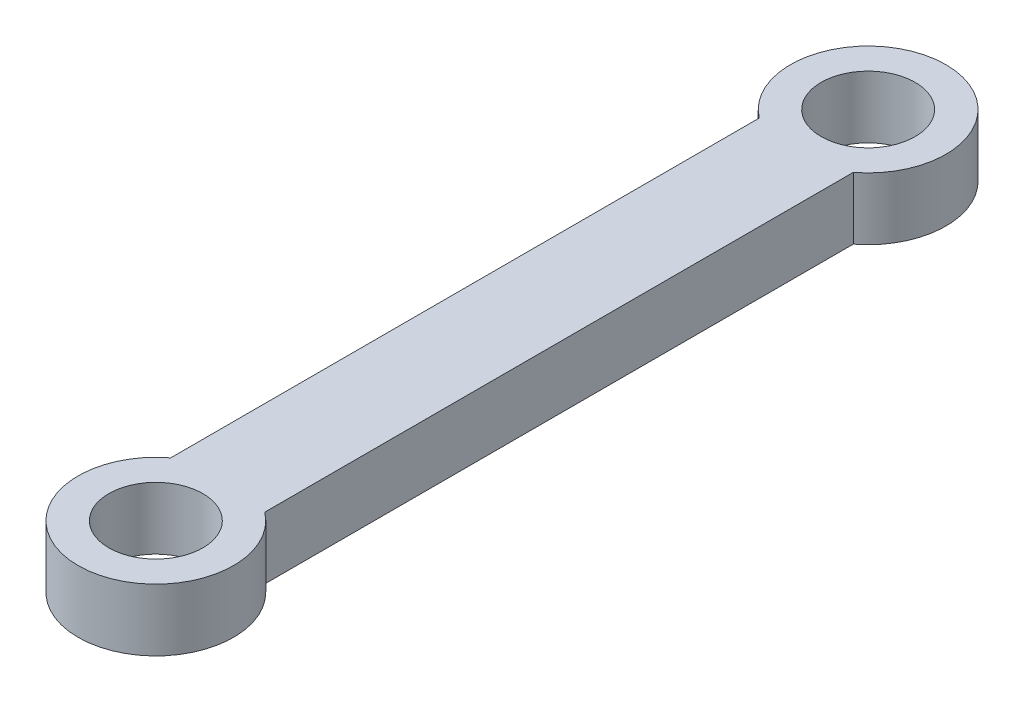
SolidWorks part; units mm, degrees
ref_plane "Front Plane" through (0, 0, 0) normal (0, 0, 1) x (1, 0, 0)
ref_plane "Top Plane" through (0, 0, 0) normal (0, 1, 0) x (1, 0, 0)
ref_plane "Right Plane" through (0, 0, 0) normal (1, 0, 0) x (0, 0, -1)
sketch "Sketch1" plane through (0, 0, 0) normal (0, 1, 0) x (1, 0, 0)
  line L0 (0, 0) -> (0, 45.82) construction
  line L1 (-3.025, 41.8389) -> (-3.025, 3.9811)
  line L2 (3.025, 41.8389) -> (3.025, 3.9811)
  circle A0 centre (0, 45.82) radius 3.025
  circle A1 centre (0, 0) radius 3.025
  arc A2 (3.025, 41.8389) -> (-3.025, 41.8389) centre (0, 45.82) ccw
  arc A3 (-3.025, 3.9811) -> (3.025, 3.9811) centre (0, 0) ccw
  dimension "D2" = 6.05
  dimension "D3" = 6.05
  dimension "D4" = 10
  dimension "D5" = 10
  dimension "D1" = 45.82
extrude "Boss-Extrude1" add sketch "Sketch1" along normal blind 4
